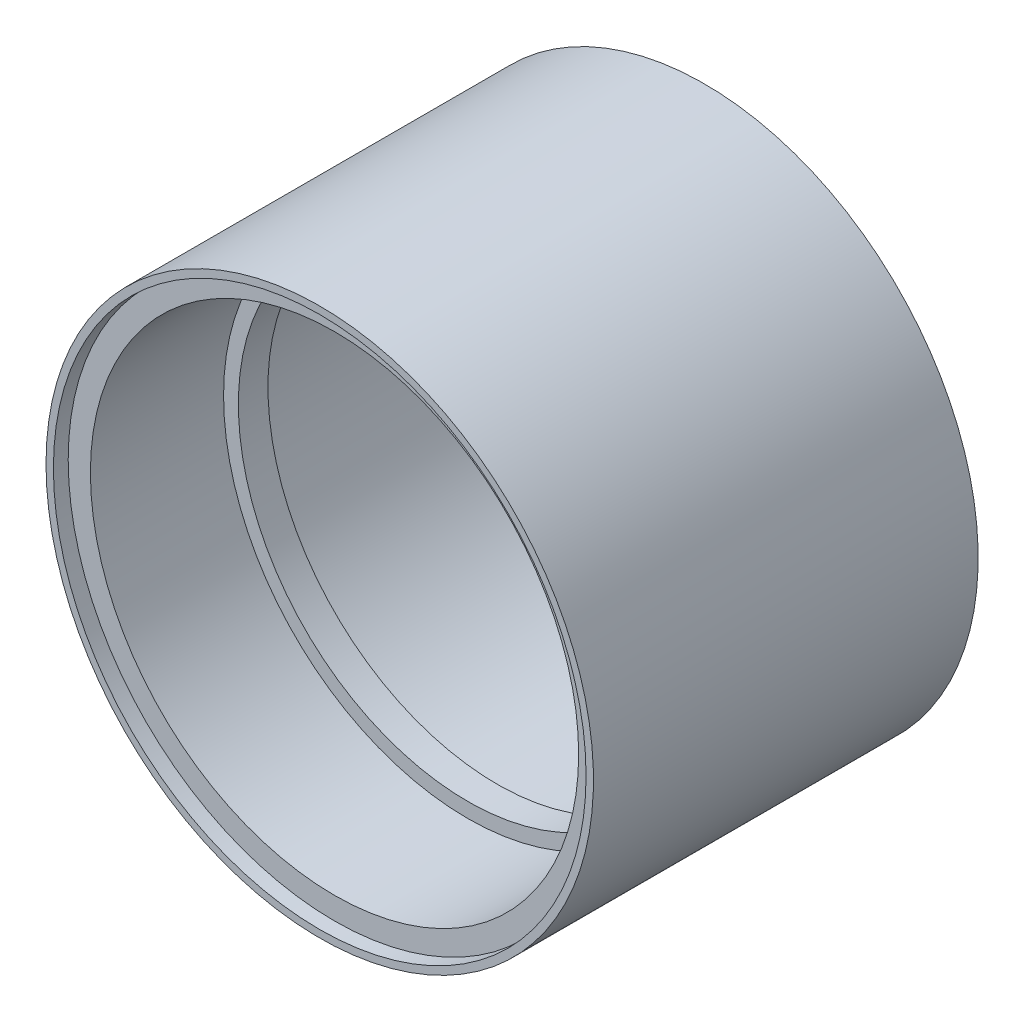
SolidWorks part; units mm, degrees
ref_plane "Front Plane" through (0, 0, 0) normal (0, 0, 1) x (1, 0, 0)
ref_plane "Top Plane" through (0, 0, 0) normal (0, 1, 0) x (1, 0, 0)
ref_plane "Right Plane" through (0, 0, 0) normal (1, 0, 0) x (0, 0, -1)
sketch "Sketch1" plane through (0, 0, 0) normal (0, 0, 1) x (1, 0, 0)
  circle A0 centre (0, 0) radius 19
  circle A1 centre (0, 0) radius 13.5
  dimension "D1" = 38
  dimension "D2" = 5.5
extrude "Boss-Extrude1" add sketch "Sketch1" along normal blind 26
sketch "Sketch2" plane through (0, 0, 0) normal (1, 0, 0) x (0, 0, -1)
  line L0 (-26, 19) -> (-26, 18.5)
  line L1 (-26, 19) -> (-26, -19) construction
  line L2 (-26, 18.5) -> (0, 18.5)
  line L3 (0, -19) -> (0, 19) construction
  line L4 (0, 18.5) -> (0, 19)
  line L5 (0, 19) -> (-26, 19)
  line L6 (0, 0) -> (-26, 0) construction
  dimension "D1" = 0.5
revolve "Cut-Revolve1" cut sketch "Sketch2" angle 360 about L6
sketch "Sketch3" plane through (0, 0, 0) normal (1, 0, 0) x (0, 0, -1)
  line L0 (0, 18) -> (0, 0)
  line L1 (-14, 15.5) -> (-14, 16.5)
  line L2 (-14, 16.5) -> (-1, 16.5)
  line L3 (-1, 16.5) -> (-1, 18)
  line L4 (-1, 18) -> (0, 18)
  line L5 (-26, 0) -> (0, 0) construction
  line L6 (-26, 18.5) -> (-26, -18.5) construction
  line L7 (0, -18.5) -> (0, 18.5) construction
  line L8 (-16, 15.5) -> (-16, 16.5)
  line L9 (-16, 16.5) -> (-25, 16.5)
  line L10 (-25, 16.5) -> (-25, 18)
  line L11 (-25, 18) -> (-26, 18)
  line L12 (-26, 18) -> (-26, 0)
  line L13 (-16, 15.5) -> (-14, 15.5)
  line L14 (-26, 0) -> (0, 0)
  dimension "D1" = 33
  dimension "D2" = 36
  dimension "D3" = 14
  dimension "D4" = 1
  dimension "D5" = 1
  dimension "D6" = 2
  dimension "D7" = 0.5
  dimension "D8" = 10
  dimension "D9" = 31
revolve "Cut-Revolve2" cut sketch "Sketch3" angle 360 about L5
